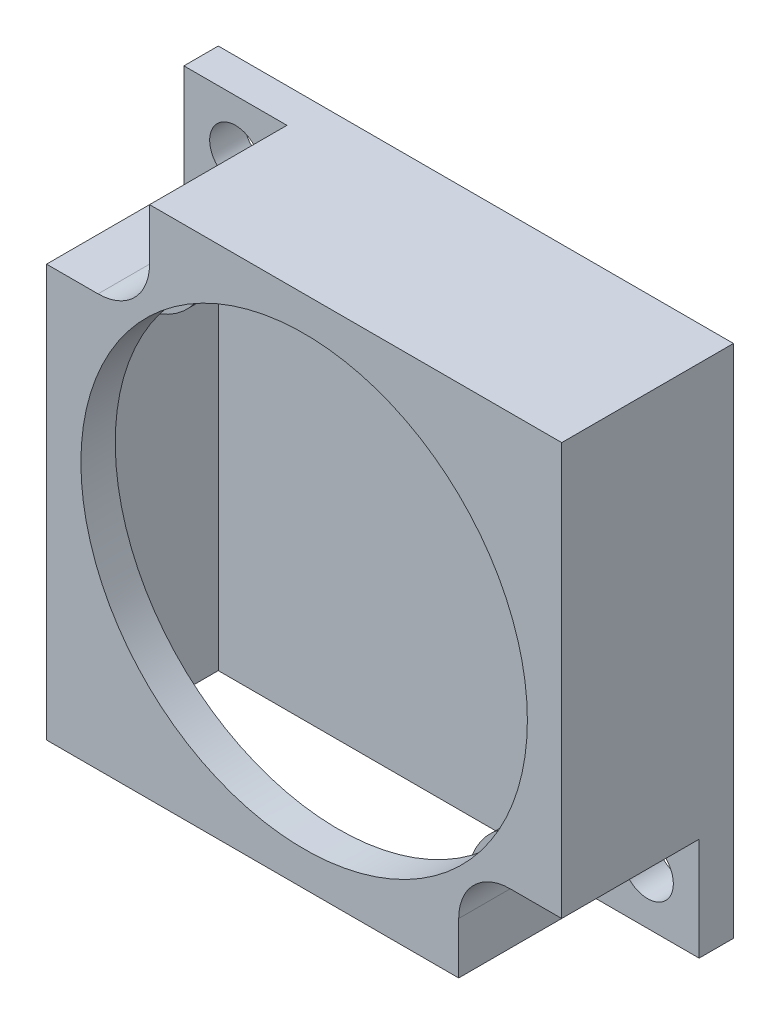
SolidWorks part; units mm, degrees
ref_plane "Plano frontal" through (0, 0, 0) normal (0, 0, 1) x (1, 0, 0)
ref_plane "Plano superior" through (0, 0, 0) normal (0, 1, 0) x (1, 0, 0)
ref_plane "Plano direito" through (0, 0, 0) normal (1, 0, 0) x (0, 0, -1)
sketch "Esboço1" plane through (0, 0, 0) normal (0, 0, 1) x (1, 0, 0)
  line L0 (-9, 12) -> (-9, 15)
  line L1 (-15, 15) -> (15, 15)
  line L2 (-15, 15) -> (-15, -15)
  line L3 (-15, -15) -> (15, -15)
  line L4 (15, 15) -> (15, -15)
  line L5 (-15, 15) -> (15, -15) construction
  line L6 (-15, -15) -> (15, 15) construction
  line L7 (-12, 9) -> (-15, 9)
  line L8 (12, -9) -> (15, -9)
  line L9 (9, -12) -> (9, -15)
  circle A0 centre (-12, 12) radius 1.5
  circle A1 centre (12, -12) radius 1.5
  arc A2 (-12, 9) -> (-9, 12) centre (-12, 12) ccw
  arc A3 (9, -12) -> (12, -9) centre (12, -12) cw
  point P0 (0, 0)
  dimension "D3" = 3
  dimension "D1" = 30
  dimension "D2" = 3
extrude "Ressalto-extrusão1" add sketch "Esboço1" along normal blind 10 contours L9 A3 L8 L4 L1 L0 A2 L7 L2 L3 region at (0, 0, 0)
extrude "Ressalto-extrusão2" add sketch "Esboço1<3>" along normal blind 2 contours L7 A2 L0 L1 L2 A0 | A3 L9 L3 L4 L8 A1 region at (-9.9387, 9.9387, 0) region at (14.9151, -12, 0)
sketch "Esboço1<3>" plane through (0, 0, 0) normal (0, 0, 1) x (1, 0, 0) same geometry as "Esboço1"
sketch "Esboço2" plane through (0, 0, 10) normal (0, 0, 1) x (1, 0, 0)
  circle A0 centre (0, 0) radius 13
  dimension "D1" = 26
extrude "Corte-extrusão1" cut sketch "Esboço2" against normal blind 2
shell "Casca1" thickness 1.5 removed face at (3, -15, 4) removed face at (13, 0, 8)
